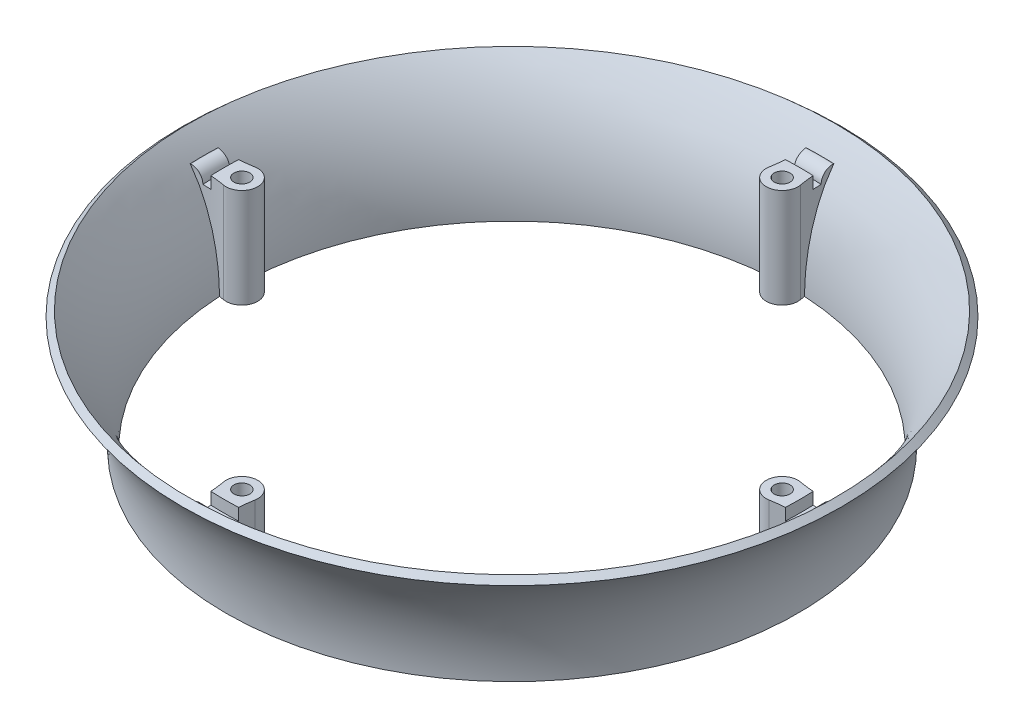
SolidWorks part; units mm, degrees
ref_plane "Front Plane" through (0, 0, 0) normal (0, 0, 1) x (1, 0, 0)
ref_plane "Top Plane" through (0, 0, 0) normal (0, 1, 0) x (1, 0, 0)
ref_plane "Right Plane" through (0, 0, 0) normal (1, 0, 0) x (0, 0, -1)
sketch "Sketch1" plane through (0, 0, 0) normal (0, 0, 1) x (1, 0, 0)
  line L0 (-25.5, 30) -> (-25.5, 0) construction
  line L1 (-25.5, 0) -> (-70, 0) construction
  line L2 (0, 0) -> (0, 30) construction
  line L3 (-70, 0) -> (-81.459, 30) construction
  arc A0 (-70, 0) -> (-81.459, 30) centre (-115, 0) ccw
  dimension "D1" = 30
  dimension "D5" = 45
  dimension "D2" = 30
  dimension "D3" = 70
  dimension "D4" = 25.5
  dimension "D7" = 30
revolve "Revolve-Thin1" add sketch "Sketch1" angle 360 about L2 wall 2
ref_plane "Plane1" through (0, 25, 0) normal (0, -1, 0) x (-1, 0, 0)
sketch "Sketch2" plane through (0, 25, 0) normal (0, -1, 0) x (-1, 0, 0)
  line L0 (-68, 0) -> (-81.459, 0) construction
  line L1 (-81.459, -4) -> (-81.459, 4)
  line L2 (-4, 81.459) -> (4, 81.459)
  line L3 (0, 68) -> (0, 81.459) construction
  line L4 (81.459, 4) -> (81.459, -4)
  line L5 (68, 0) -> (81.459, 0) construction
  line L6 (4, -81.459) -> (-4, -81.459)
  line L7 (0, -68) -> (0, -81.459) construction
  circle A0 centre (-68, 0) radius 2
  arc A1 (-68.6908, -3.9399) -> (-68.6908, 3.9399) centre (-68, 0) ccw
  circle A2 centre (0, 0) radius 81.459 construction
  arc A3 (-81.3616, 3.9821) -> (-81.3616, -3.9821) centre (0, 0) ccw
  arc A4 (-68.6908, 3.9399) -> (-81.459, 4) centre (-74.9081, 39.399) cw
  arc A5 (-68.6908, -3.9399) -> (-81.459, -4) centre (-74.9081, -39.399) ccw
  arc A6 (3.9399, 68.6908) -> (4, 81.459) centre (39.399, 74.9081) cw
  arc A7 (-3.9399, 68.6908) -> (3.9399, 68.6908) centre (0, 68) ccw
  circle A8 centre (0, 68) radius 2
  arc A9 (-3.9399, 68.6908) -> (-4, 81.459) centre (-39.399, 74.9081) ccw
  arc A10 (68.6908, -3.9399) -> (81.459, -4) centre (74.9081, -39.399) cw
  arc A11 (68.6908, 3.9399) -> (68.6908, -3.9399) centre (68, 0) ccw
  circle A12 centre (68, 0) radius 2
  arc A13 (68.6908, 3.9399) -> (81.459, 4) centre (74.9081, 39.399) ccw
  arc A14 (-3.9399, -68.6908) -> (-4, -81.459) centre (-39.399, -74.9081) cw
  arc A15 (3.9399, -68.6908) -> (-3.9399, -68.6908) centre (0, -68) ccw
  circle A16 centre (0, -68) radius 2
  arc A17 (3.9399, -68.6908) -> (4, -81.459) centre (39.399, -74.9081) ccw
  point P10 (-81.459, 0)
  dimension "D1" = 4
  dimension "D2" = 8
  dimension "D4" = 36
  dimension "D5" = 68
  dimension "D3" = 8
  dimension "D6" = 4
extrude "Boss-Extrude1" add sketch "Sketch2" along normal up to surface (25 mm away) contours A17 A15 A14 L6 A16 | A13 A11 A10 L4 A12 | A9 A7 A6 L2 A8 | A5 A1 A4 A3 A0 region at (73.5344, 25, 0) region at (0, 25, -73.5531) region at (-73.5531, 25, 0) region at (0, 25, 73.5531) up to face at (0, 0, -72)
sketch "Sketch3" plane through (0, 0, 0) normal (0, 0, 1) x (1, 0, 0)
  line L0 (-72, 0) -> (-99.1272, 0)
  line L1 (-99.1272, 0) -> (-99.1272, 28.6667)
  line L3 (-99.1272, 28.6667) -> (-82.9497, 28.6667)
  arc A0 (-70, 0) -> (-81.459, 30) centre (-115, 0) ccw construction
  arc A4 (-72, 0) -> (-82.9497, 28.6667) centre (-115, 0) ccw
  arc A5 (-72, 0) -> (-82.9497, 28.6667) centre (-115, 0) ccw
  dimension "D1" = 2
revolve "Cut-Revolve1" cut sketch "Sketch3" angle 360 about L2
sketch "Sketch4" plane through (0, 25, 0) normal (0, 1, 0) x (1, 0, 0)
  circle A0 centre (0, 0) radius 74.5
  circle A1 centre (0, 0) radius 72.4
  dimension "D1" = 149
  dimension "D2" = 2.1
extrude "Cut-Extrude1" cut sketch "Sketch4" against normal blind 3
fillet "Fillet1" radius 3 4 edges at (-74.5, 25, 0) (0, 25, 74.5) (74.5, 25, 0) (0, 25, -74.5)
